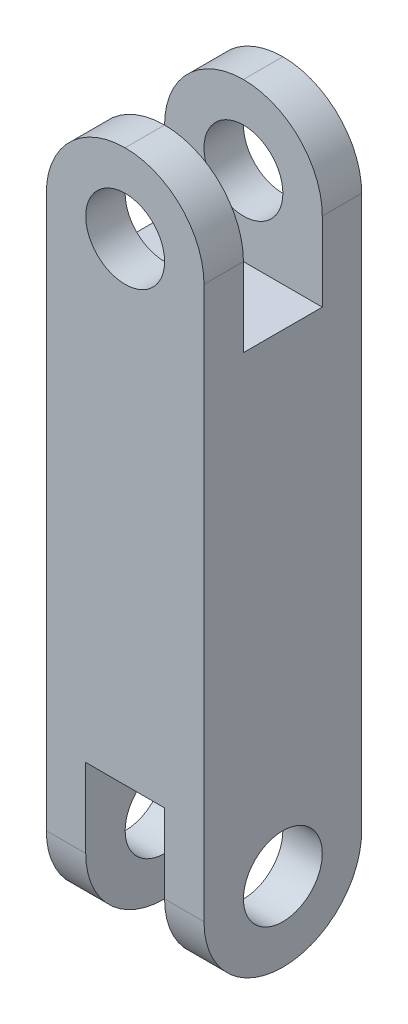
SolidWorks part; units mm, degrees
material "7075-T6 (SN)"
ref_plane "Front Plane" through (0, 0, 0) normal (0, 0, 1) x (1, 0, 0)
ref_plane "Top Plane" through (0, 0, 0) normal (0, 1, 0) x (1, 0, 0)
ref_plane "Right Plane" through (0, 0, 0) normal (1, 0, 0) x (0, 0, -1)
sketch "Sketch2" plane through (0, 0, 0) normal (0, 1, 0) x (1, 0, 0)
  line L1 (-50.8, -50.8) -> (50.8, -50.8)
  line L2 (-50.8, -50.8) -> (-50.8, 50.8)
  line L3 (-50.8, 50.8) -> (50.8, 50.8)
  line L4 (50.8, -50.8) -> (50.8, 50.8)
  line L5 (-50.8, -50.8) -> (50.8, 50.8) construction
  line L6 (-50.8, 50.8) -> (50.8, -50.8) construction
  point P0 (0, 0)
  dimension "D1" = 101.6
  dimension "D2" = 101.6
extrude "Boss-Extrude1" add sketch "Sketch2" along normal blind 457.2
sketch "Sketch3" plane through (0, 0, 0) normal (0, 0, 1) x (1, 0, 0)
  line L0 (-50.8, 0) -> (50.8, 0) construction
  line L1 (-25.4, 0) -> (25.4, 0)
  line L2 (-25.4, 0) -> (-25.4, 101.6)
  line L3 (-25.4, 101.6) -> (25.4, 101.6)
  line L4 (25.4, 0) -> (25.4, 101.6)
  line L5 (-50.8, 457.2) -> (-50.8, 0) construction
  line L6 (-50.8, 457.2) -> (50.8, 457.2) construction
  circle A0 centre (0, 406.4) radius 25.4
  dimension "D4" = 50.8
  dimension "D1" = 50.8
  dimension "D2" = 101.6
  dimension "D3" = 25.4
  dimension "D5" = 50.8
extrude "Cut-Extrude1" cut sketch "Sketch3" against normal through all both and the other way through all
fillet "Fillet1" radius 50.8 6 edges at (-38.1, 0, -50.8) (-38.1, 0, 50.8) (38.1, 0, -50.8) (38.1, 0, 50.8) (-50.8, 457.2, 0) (50.8, 457.2, 0)
sketch "Sketch4" plane through (50.8, 0, 0) normal (1, 0, 0) x (0, 0, -1)
  line L1 (-25.4, 355.6) -> (25.4, 355.6)
  line L2 (-25.4, 355.6) -> (-25.4, 457.2)
  line L3 (-25.4, 457.2) -> (25.4, 457.2)
  line L4 (25.4, 355.6) -> (25.4, 457.2)
  line L6 (-50.8, 457.2) -> (-50.8, 406.4) construction
  circle A0 centre (0, 50.8) radius 25.4
  dimension "D1" = 50.8
  dimension "D2" = 50.8
  dimension "D3" = 50.8
  dimension "D4" = 25.4
  dimension "D5" = 101.6
  dimension "D6" = 457.2
extrude "Cut-Extrude2" cut sketch "Sketch4" against normal through all both
